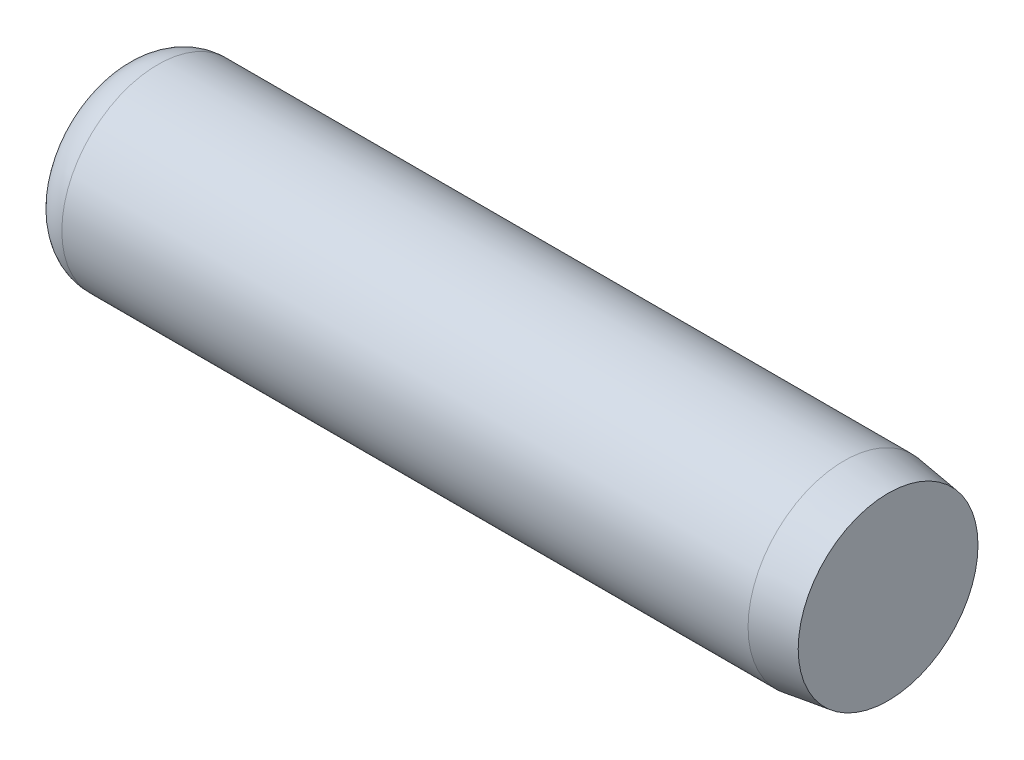
SolidWorks part; units mm, degrees
ref_plane "Plane1" through (0, 0, 0) normal (0, 0, 1) x (1, 0, 0)
ref_plane "Plane2" through (0, 0, 0) normal (0, 1, 0) x (1, 0, 0)
ref_plane "Plane3" through (0, 0, 0) normal (1, 0, 0) x (0, 0, -1)
sketch "Sketch1" plane through (0, 0, 0) normal (0, 0, 1) x (1, 0, 0)
  line L1 (-6.35, 0) -> (128.8927, 0) construction
  line L2 (0, 0) -> (101.6, 0)
  line L3 (101.6, 0) -> (101.6, 11.8833)
  line L4 (101.6, 11.8833) -> (95.7888, 12.7)
  line L5 (95.7888, 12.7) -> (5.08, 12.7)
  line L6 (0, 7.62) -> (0, 0)
  arc A0 (5.08, 12.7) -> (0, 7.62) centre (5.08, 7.62) ccw
  dimension "fillet" = 5.08
  dimension "D3" = 8
  dimension "Diameter" = 25.4
  dimension "Length" = 101.6
  dimension "diameter_B" = 23.7666
revolve "Base-Revolve" add sketch "Sketch1" angle 360 about L1
